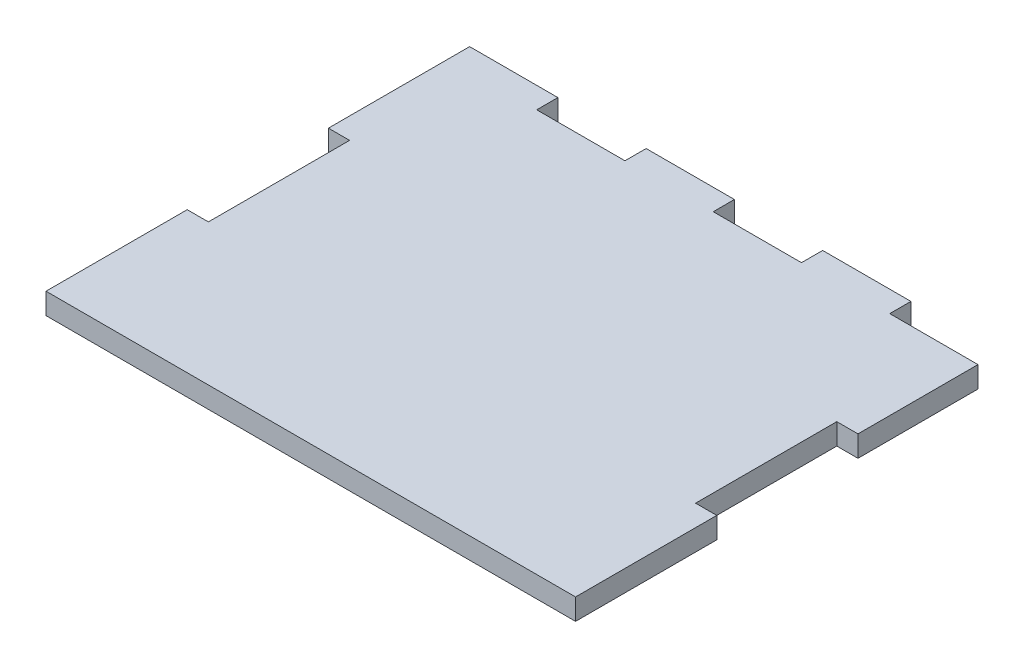
SolidWorks part; units mm, degrees
ref_plane "Front Plane" through (0, 0, 0) normal (0, 0, 1) x (1, 0, 0)
ref_plane "Top Plane" through (0, 0, 0) normal (0, 1, 0) x (1, 0, 0)
ref_plane "Right Plane" through (0, 0, 0) normal (1, 0, 0) x (0, 0, -1)
sketch "Sketch1" plane through (0, 0, 0) normal (0, 1, 0) x (1, 0, 0)
  line L1 (150, 80) -> (0, 80)
  line L2 (150, 80) -> (150, 200)
  line L3 (150, 200) -> (0, 200)
  line L4 (0, 80) -> (0, 200)
  point P4 (0, 0)
  dimension "D1" = 150
  dimension "D2" = 120
extrude "Boss-Extrude1" add sketch "Sketch1" along normal blind 6
sketch "Sketch2" plane through (0, 6, 0) normal (0, 1, 0) x (1, 0, 0)
  line L5 (0, 200) -> (0, 80) construction
  line L14 (25, 194) -> (25, 200)
  line L15 (25, 194) -> (50, 194)
  line L16 (50, 194) -> (50, 200)
  line L17 (25, 200) -> (50, 200)
  line L18 (75, 194) -> (75, 200)
  line L19 (75, 194) -> (100, 194)
  line L20 (100, 194) -> (100, 200)
  line L21 (75, 200) -> (100, 200)
  line L22 (125, 194) -> (125, 200)
  line L23 (125, 194) -> (150, 194)
  line L24 (150, 194) -> (150, 200)
  line L25 (125, 200) -> (150, 200)
  line L26 (150, 200) -> (0, 200) construction
  line L27 (0, 160) -> (6, 160)
  line L28 (0, 160) -> (0, 120)
  line L29 (0, 120) -> (6, 120)
  line L30 (6, 160) -> (6, 120)
  line L31 (144, 160) -> (144, 120)
  line L32 (144, 160) -> (150, 160)
  line L33 (150, 160) -> (150, 120)
  line L34 (144, 120) -> (150, 120)
  line L45 (144, 80) -> (144, 40) [skipped]
  line L46 (144, 80) -> (150, 80) [skipped]
  line L47 (150, 80) -> (150, 40) [skipped]
  line L48 (144, 40) -> (150, 40) [skipped]
  line L49 (0, 80) -> (0, 40) [skipped]
  line L50 (0, 80) -> (6, 80) [skipped]
  line L51 (6, 80) -> (6, 40) [skipped]
  line L52 (0, 40) -> (6, 40) [skipped]
  dimension "D6" = 40
  dimension "D7" = 40
  dimension "D8" = 6
  dimension "D9" = 2
  dimension "D10" = 2
extrude "Cut-Extrude1" cut sketch "Sketch2" against normal blind 6
